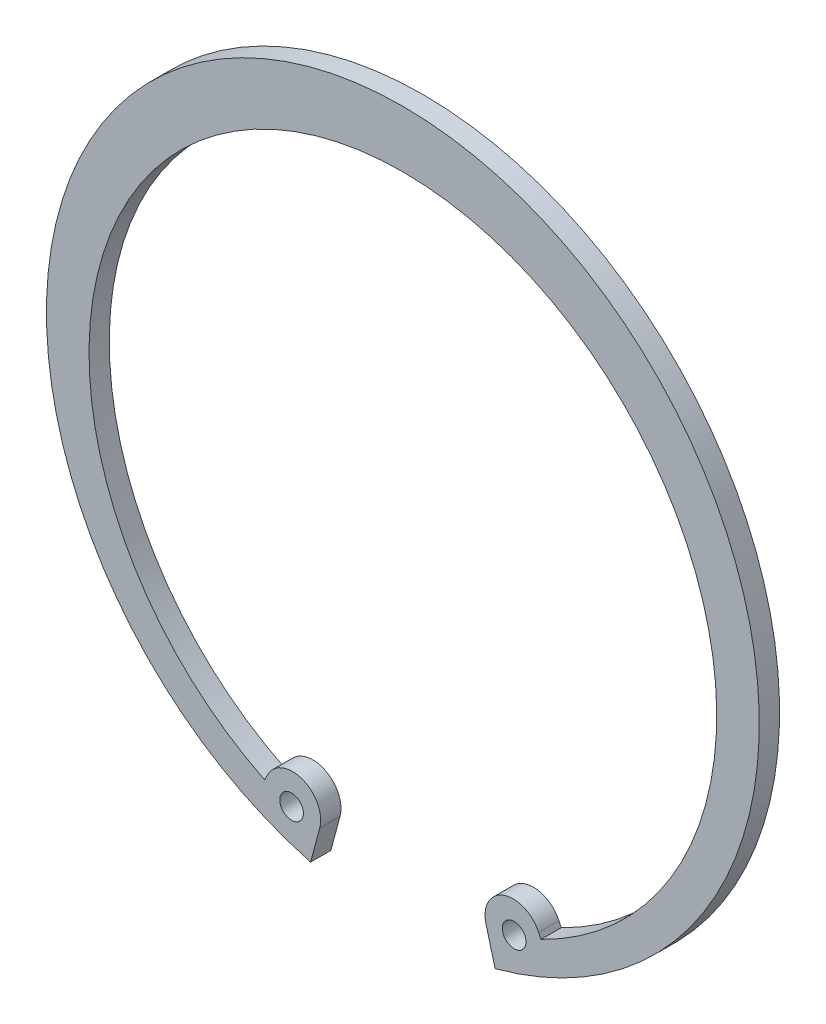
SolidWorks part; units mm, degrees
material "Steel Spring  ASTM A228 "
ref_plane "Front" through (0, 0, 0) normal (0, 0, 1) x (1, 0, 0)
ref_plane "Top" through (0, 0, 0) normal (0, 1, 0) x (1, 0, 0)
ref_plane "Right" through (0, 0, 0) normal (1, 0, 0) x (0, 0, -1)
sketch "Layout" plane through (0, 0, 0) normal (0, 0, 1) x (1, 0, 0)
  line L0 (0, 0) -> (13.6527, -50.9526) construction
  line L1 (0, 0) -> (0, -2.175) construction
  line L2 (0, 0) -> (22.2977, -47.8056) construction
  line L3 (0, 52.75) -> (0, 48.55) construction
  line L4 (0, -52.75) -> (0, -48.55) construction
  line L5 (0, 48.55) -> (0, 44.35) construction
  line L6 (14.897, -40.9229) -> (0, 0) construction
  line L7 (14.897, -40.9229) -> (18.044, -49.5679) construction
  line L8 (-52.75, 0) -> (-49.75, 0) construction
  line L9 (11.3147, -42.2269) -> (11.9305, -44.5252) construction
  line L10 (11.9305, -44.5252) -> (12.5463, -46.8235) construction
  line L11 (22.2977, -47.8056) -> (13.6527, -50.9526) construction
  line L12 (11.3147, -42.2269) -> (18.4792, -39.6189) construction
  circle A0 centre (0, 0) radius 52.75 construction
  circle A1 centre (0, -2.1) radius 46.45 construction
  circle A3 centre (16.4705, -45.2454) radius 1.75 construction
  dimension "D1" = 15
sketch "Sketch2" plane through (0, 0, 0) normal (0, 0, 1) x (1, 0, 0)
  line L0 (0, 0) -> (22.2977, -47.8056) construction
  line L1 (0, 0) -> (13.6527, -50.9526) construction
  line L2 (18.4792, -39.6189) -> (20.4356, -43.8132)
  line L3 (11.3147, -42.2269) -> (13.6527, -50.9526)
  line L4 (0, 0) -> (0, -2.175) construction
  line L5 (0, 7.7639) -> (0, -6.0981) construction
  line L6 (0, 52.75) -> (0, 44.35)
  line L7 (11.3147, -42.2269) -> (18.4792, -39.6189) construction
  line L8 (11.3147, -42.2269) -> (18.4792, -39.6189)
  circle A0 centre (0, -2.1) radius 46.45 construction
  arc A1 (20.4356, -43.8132) -> (0, 44.35) centre (0, -2.1) ccw
  circle A2 centre (0, 0) radius 52.75 construction
  circle A3 centre (16.4705, -45.2454) radius 1.75 construction
  arc A4 (13.6527, -50.9526) -> (0, 52.75) centre (0, 0) ccw
  circle A7 centre (16.4705, -45.2454) radius 1.75
extrude "Boss-Extrude1" add sketch "Sketch2" along normal blind 3
fillet "Fillet1" 2 edges at (18.4792, -39.6189, 1.5) (11.3147, -42.2269, 1.5) type full round first side face at (19.4574, -41.716, 1.5) second side face at (12.4837, -46.5898, 1.5) middle face at (14.897, -40.9229, 1.5)
mirror "Mirror1" about plane through (0, 52.75, 3) normal (1, 0, 0) of bodies 109
equation "\"D1@Boss-Extrude1\"=\"thickness@Layout\""
